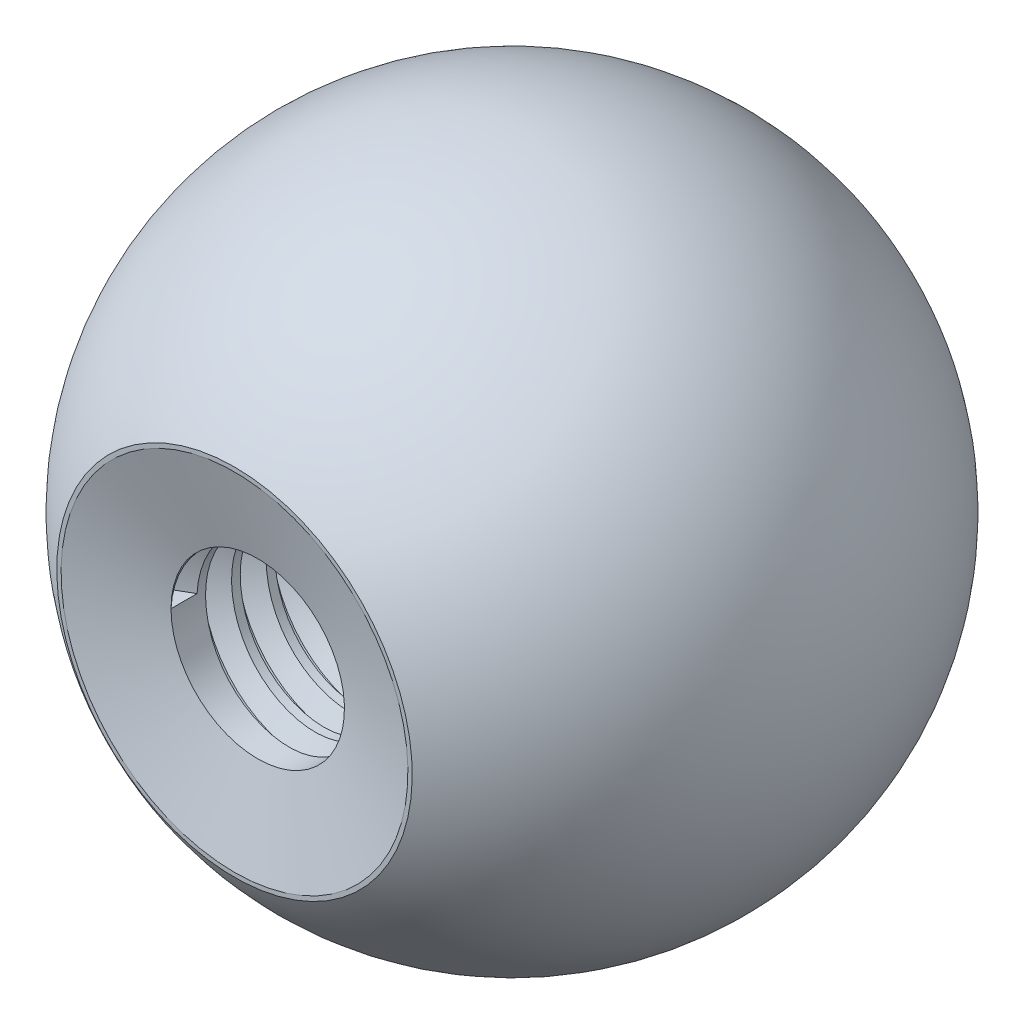
SolidWorks part; units mm, degrees
ref_plane "Front Plane" through (0, 0, 0) normal (0, 0, 1) x (1, 0, 0)
ref_plane "Top Plane" through (0, 0, 0) normal (0, 1, 0) x (1, 0, 0)
ref_plane "Right Plane" through (0, 0, 0) normal (1, 0, 0) x (0, 0, -1)
sketch "Sketch33" plane through (0, 0, 0) normal (0, 0, 1) x (1, 0, 0)
  line L0 (0, 4.75) -> (0, -4.75)
  arc A0 (0, 4.75) -> (0, -4.75) centre (0, 0) ccw
  dimension "D1" = 9.5
revolve "Revolve1" add sketch "Sketch33" angle 360 about L0
sketch "Sketch34" plane through (0, 0, 0) normal (1, 0, 0) x (0, 0, -1)
  line L1 (-6.6479, 3.8829) -> (-4, 3.8829)
  line L2 (-6.6479, 3.8829) -> (-6.6479, -4.2908)
  line L3 (-6.6479, -4.2908) -> (-4, -4.2908)
  line L4 (-4, 3.8829) -> (-4, -4.2908)
  point P4 (-4, -0.2039)
  dimension "D1" = 4
extrude "Cut-Extrude1" cut sketch "Sketch34" against normal mid plane 10
sketch "Sketch38" plane through (0, 0, 4) normal (0, 0, 1) x (1, 0, 0)
  circle A0 centre (0, 0) radius 2.5617 construction
  circle A1 centre (0, 0) radius 2.5617 construction
hole_wizard "CSK for M3 Flat Head Machine Screw1" positions "3DSketch3" profile "Sketch40" countersink size "M3" standard "ANSI Metric"
sketch3d "3DSketch3"
  point P0 (0, 0, 4)
sketch "Sketch40" plane through (0, 0, 4) normal (1, 0, 0) x (0, -1, 0)
  line L0 (0, 0) -> (0, 5.7511)
  line L1 (0, 5.7511) -> (1.25, 5)
  line L2 (1.25, 5) -> (1.25, 0.3349)
  line L3 (1.25, 0.3349) -> (2.5, 0)
  line L5 (2.5, 0) -> (0, 0)
  line L6 (-1.25, 0.3349) -> (-2.5, 0) construction
  line L10 (0, 5.7511) -> (-1.25, 5) construction
  line L11 (0, -6.35) -> (0, 107.95) construction
  dimension "Hole Dia." = 2.5
  dimension "Hole Depth" = 5
  dimension "Near C'Sink Dia." = 5
  dimension "Near C'Sink Angle" = 150
  dimension "Drill Angle" = 118
thread "Thread1" pitch 0.5 method cut profile "Thread Profile1" start angle 0, offset 0, length 5, pitch 0.5, diameter 2.5
ref_plane "Plane1" through (-1.25, 0, 3.6651) normal (0, -1, 0) x (-1, 0, 0)
sketch "Thread Profile1" plane through (-1.25, 0, 3.6651) normal (0, -1, 0) x (-1, 0, 0)
  line L0 (0, 0) -> (0, 0.5) construction
  line L1 (0, 0) -> (0.2706, 0.1562)
  line L2 (0.2706, 0.1562) -> (0.2706, 0.2187)
  line L3 (0.2706, 0.2187) -> (0, 0.375)
  line L4 (0.2706, 0.1875) -> (0, 0.1875) construction
  line L11 (0, 0) -> (0, 0.375)
  point P2 (0, 0)
  dimension "Pitch" = 0.5
  dimension "Profile_Angle" = 60
  dimension "Profile_Land" = 0.0625
  dimension "Profile_Height" = 0.2706
equation "\"D1@Sketch33\"=\"markerDiam@ring assembly.Assembly\""
equation "\"D1@Sketch34\"=\"markerDiam@ring assembly.Assembly\"/2-\"markerCapHeight@ring assembly.Assembly\""
